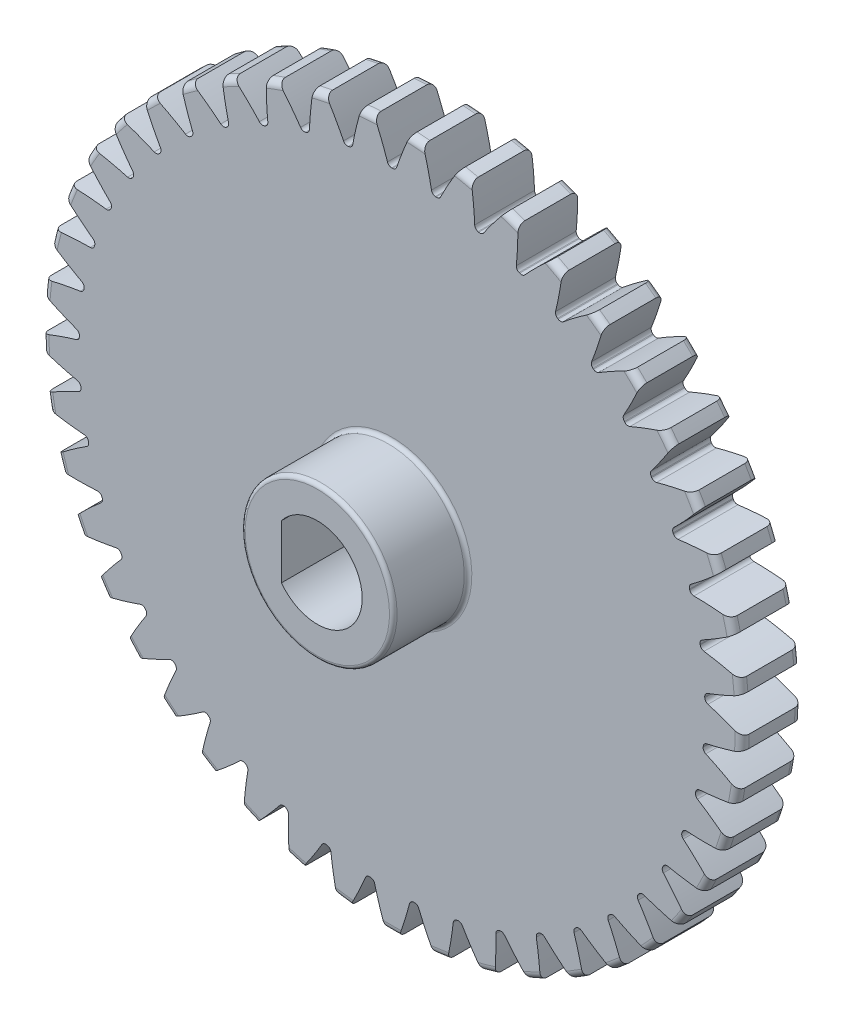
SolidWorks part; units mm, degrees
ref_plane "Front Plane" through (0, 0, 0) normal (0, 0, 1) x (1, 0, 0)
ref_plane "Top Plane" through (0, 0, 0) normal (0, 1, 0) x (1, 0, 0)
ref_plane "Right Plane" through (0, 0, 0) normal (1, 0, 0) x (0, 0, -1)
sketch "Sketch1" plane through (0, 0, 0) normal (0, 0, 1) x (1, 0, 0)
  line L0 (-571.5, 0) -> (571.5, 0) construction
  circle A0 centre (0, 0) radius 23.4061 construction
  circle A1 centre (0, 0) radius 22.4155 construction
  circle A2 centre (0, 0) radius 20.9155 construction
  circle A3 centre (0, 0) radius 11.684 construction
  circle A4 centre (0, 0) radius 6.35 construction
  dimension "D2" = 0.9906
  dimension "D3" = 2.4906
  dimension "D1" = 2.4906
sketch "Sketch2" plane through (0, 0, 0) normal (1, 0, 0) x (0, 0, -1)
  line L0 (0, 0) -> (-4.0005, 0) construction
  line L1 (-4.0005, 0) -> (-8.9992, 0) construction
  dimension "Overall Width" = 8.9992
  dimension "Face Width" = 4.0005
sketch "Sketch4" plane through (0, 0, 0) normal (1, 0, 0) x (0, 0, -1)
  line L0 (-8.9992, 6.35) -> (-8.9992, 11.684)
  line L1 (-8.9992, 11.684) -> (-4.0005, 11.684)
  line L2 (-4.0005, 11.684) -> (-4.0005, 23.4061)
  line L3 (-4.0005, 23.4061) -> (0, 23.4061)
  line L4 (0, 23.4061) -> (0, 6.35)
  line L5 (-4.0005, 11.684) -> (-4.0005, 0) construction
  line L6 (0, 23.4061) -> (0, -23.4061) construction
  line L7 (-4.0005, 11.684) -> (0, 11.684) construction
  line L12 (-8.9992, 6.35) -> (0, 6.35)
revolve "Revolve1" add sketch "Sketch4" angle 360 about L1
fillet "Fillet2" radius 0.4681 4 edges at (0, 11.684, 8.9992) (0, 11.684, 4.0005) (0, 23.4061, 4.0005) (0, 23.4061, 0)
sketch "Sketch7" plane through (0, 0, 4.0005) normal (0, 0, 1) x (1, 0, 0)
  line L0 (0, 0) -> (0, 23.4061) construction
  line L1 (0.7823, 22.4018) -> (1.1761, 23.3765) construction
  line L3 (1.6327, 23.3491) -> (1.5636, 22.3609) construction
  line L4 (1.5636, 22.3609) -> (1.459, 20.8645) construction
  line L5 (0, 0) -> (1.459, 20.8645) construction
  line L6 (0.7823, 22.4018) -> (0, 0) construction
  line L7 (0.7823, 22.4018) -> (0.8169, 23.3918) construction
  line L8 (0.7823, 22.4018) -> (0, 0) construction
  circle A0 centre (0, 0) radius 23.4061 construction
  arc A1 (-0.0253, 20.9155) -> (0.0253, 20.9155) centre (0, 0) cw
  circle A2 centre (0, 0) radius 20.9155 construction
  arc A3 (-0.7823, 22.4018) -> (0.7823, 22.4018) centre (0, 0) cw construction
  circle A4 centre (0, 0) radius 22.4155 construction
  arc A5 (2.0623, 23.3151) -> (1.2026, 23.3752) centre (0, 0) ccw construction
  arc A6 (0.7823, 22.4018) -> (2.3431, 22.2927) centre (0, 0) cw construction
  arc A7 (-1.2026, 23.3752) -> (1.2026, 23.3752) centre (0, 0) cw
  arc A8 (0.3091, 21.1195) -> (1.2026, 23.3752) centre (21.5656, 14.0049) cw
  arc A9 (-0.3091, 21.1195) -> (-1.2026, 23.3752) centre (-21.5656, 14.0049) ccw
  arc A10 (-0.0253, 20.9155) -> (-0.3091, 21.1195) centre (-0.0257, 21.2144) cw
  arc A11 (0.0253, 20.9155) -> (0.3091, 21.1195) centre (0.0257, 21.2144) ccw
  point P26 (-0.2415, 20.9141)
  point P29 (0.2415, 20.9141)
  dimension "D4" = 0.2989
  dimension "D5" = 22.4155
  dimension "D3" = 20
  dimension "D1" = 3.1298
  dimension "D2" = 1.5649
extrude "Cut-Extrude2" cut sketch "Sketch7" against normal through all
pattern_circular "CirPattern1" count 45 over 360 about axis through (0, 0, 8.9992) along (0, 0, -1) of "Cut-Extrude2"
sketch "Sketch8" plane through (0, 0, 8.9992) normal (0, 0, 1) x (1, 0, 0)
  line L0 (-2.4, 1.8) -> (-2.4, -1.8)
  arc A0 (-2.4, -1.8) -> (-2.4, 1.8) centre (0, 0) ccw
  circle A1 centre (0, 0) radius 8.8024
  dimension "D1" = 6
  dimension "D2" = 2.4
extrude "Boss-Extrude1" add sketch "Sketch8" against normal up to surface (8.9992 mm away) up to face at (0, 0, 0)
sketch "Sketch9" plane through (0, 0, 8.9992) normal (0, 0, 1) x (1, 0, 0)
  circle A0 centre (0, 0) radius 5.08
  circle A1 centre (0, 0) radius 18.481
  dimension "D1" = 10.16
extrude "Cut-Extrude3" cut sketch "Sketch9" against normal up to surface (4.9987 mm away) up to face at (0, 0, 4.0005)
fillet "Fillet3" radius 0.254 2 edges at (5.08, 0, 8.9992) (0, -5.08, 4.0005)
sketch "Sketch10" plane through (0, 0, 0) normal (0, 0, -1) x (-1, 0, 0)
  circle A0 centre (0, 0) radius 16.1798
  circle A1 centre (0, 0) radius 20.9155
  circle A2 centre (0, 0) radius 18.5476
  dimension "D1" = 41.831
  dimension "D2" = 32.3596
  dimension "D3" = 37.0953
sketch "Sketch11" plane through (0, 0, 0) normal (0, 0, -1) x (-1, 0, 0)
  line L0 (2.4, 1.8) -> (2.4, -1.8) construction
  line L1 (2.4, 1.8) -> (2.4, -1.8)
  line L2 (2.4, 0) -> (-9.0493, 0)
ref_plane "Plane1" through (0, 0, 0) normal (0, 1, 0) x (1, 0, 0)
sketch "Sketch12" plane through (0, 0, 0) normal (0, 1, 0) x (1, 0, 0)
  line L0 (0, 0) -> (0, 19.1506)
ref_axis "Axis1" through (0, 0, 0) along (0, 0, -1)
equation "\"D1@Sketch1\"=2.5*(\"Pitch Dia.@Sketch1\"/\"Number of Teeth@Sketch1\")"
equation "\"D1@CirPattern1\"=\"Number of Teeth@Sketch1\""
equation "\"D1@Fillet2\"=\"OD@Sketch1\"*.01"
equation "\"D1@Sketch7\"=3.14159*(\"Pitch Dia.@Sketch1\"/\"Number of Teeth@Sketch1\")"
equation "\"D2@Sketch7\"=\"D1@Sketch7\"/2"
equation "\"D4@Sketch7\"=\"D1@Sketch7\"*.0955"
equation "\"D5@Sketch7\"=\"Pitch Dia.@Sketch1\"/2"
equation "\"D3@Sketch10\"=(\"D2@Sketch10\"+\"D1@Sketch10\")/2"
equation "\"D1@Sketch8\"=6/25.4"
equation "\"D2@Sketch8\"=(\"D1@Sketch8\"/2)*0.8"
